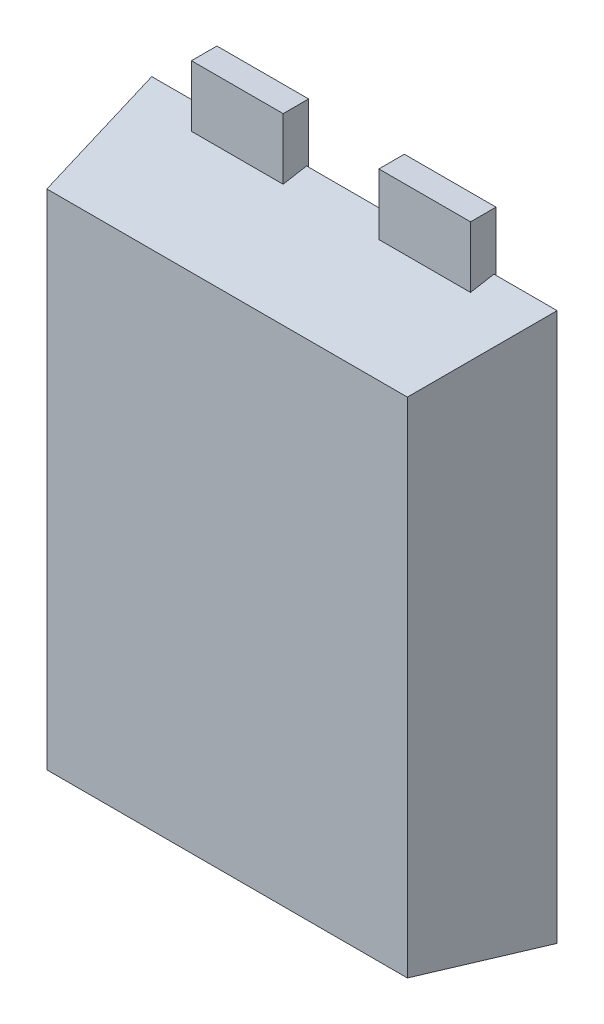
SolidWorks part; units mm, degrees
ref_plane "Front Plane" through (0, 0, 0) normal (0, 0, 1) x (1, 0, 0)
ref_plane "Top Plane" through (0, 0, 0) normal (0, 1, 0) x (1, 0, 0)
ref_plane "Right Plane" through (0, 0, 0) normal (1, 0, 0) x (0, 0, -1)
sketch "Sketch2" plane through (0, 0, 0) normal (0, 0, 1) x (1, 0, 0)
  line L22 (-1.525, 1.15) -> (-1.525, -2.4)
  line L23 (-1.525, -2.4) -> (-0.9, -2.4)
  line L24 (-0.9, -2.4) -> (-0.9, -3.25)
  line L25 (-0.9, -3.25) -> (-0.55, -3.25)
  line L26 (-0.55, -3.25) -> (-0.55, -3.05)
  line L27 (-0.55, -3.05) -> (0.55, -3.05)
  line L28 (0.55, -3.05) -> (0.55, -3.25)
  line L29 (0.55, -3.25) -> (0.9, -3.25)
  line L30 (0.9, -3.25) -> (0.9, -2.4)
  line L31 (0.9, -2.4) -> (1.525, -2.4)
  line L32 (1.525, -2.4) -> (1.525, 1.15)
  line L33 (1.525, 1.15) -> (-1.525, 1.15)
  line L34 (0, -0.9337) -> (0, 4.9794) construction
  line L35 (-1.37, 3.25) -> (-0.47, 3.25)
  line L36 (-1.37, 3.25) -> (-1.37, 2.4)
  line L37 (-1.37, 2.4) -> (-0.47, 2.4)
  line L38 (-0.47, 3.25) -> (-0.47, 2.4)
  line L39 (0.47, 3.25) -> (1.37, 3.25)
  line L40 (0.47, 3.25) -> (0.47, 2.4)
  line L41 (0.47, 2.4) -> (1.37, 2.4)
  line L42 (1.37, 3.25) -> (1.37, 2.4)
  point P2 (0, 1.15)
  point P24 (-0.92, 3.25)
  point P25 (0.92, 3.25)
  dimension "D1" = 3.05
  dimension "D2" = 3.55
  dimension "D3" = 0.85
  dimension "D4" = 1.8
  dimension "D5" = 0.35
  dimension "D6" = 0.2
  dimension "D7" = 3.25
  dimension "D8" = 1.25
  dimension "D9" = 6.5
  dimension "D10" = 0.9
  dimension "D11" = 1.84
extrude "Boss-Extrude1" add sketch "Sketch2" along normal blind 0.25
ref_plane "Plane1" through (0, 0, 0.02) normal (0, 0, 1) x (1, 0, 0)
sketch "Sketch3" plane through (0, 0, 0.02) normal (0, 0, 1) x (1, 0, 0)
  line L0 (-0.47, 3.25) -> (-1.37, 3.25) construction
  line L1 (-1.99, 2.69) -> (1.99, 2.69)
  line L2 (-1.99, 2.69) -> (-1.99, -2.69)
  line L3 (-1.99, -2.69) -> (1.99, -2.69)
  line L4 (1.99, 2.69) -> (1.99, -2.69)
  point P9 (0, 2.69)
  dimension "D1" = 5.38
  dimension "D2" = 3.98
  dimension "D3" = 0.56
extrude "Boss-Extrude2" add sketch "Sketch3" along normal blind 1.25
chamfer "Chamfer6" distance 1.25 angle 10 1 edges at (0, -2.69, 1.27) first distance on face at (0, -2.69, 0.39)
chamfer "Chamfer7" distance 1.25 angle 10 1 edges at (0, 2.69, 1.27) first distance on face at (0, 2.69, 0.645)
chamfer "Chamfer8" distance 1.25 angle 10 2 edges at (-1.99, 0, 1.27) (1.99, 0, 1.27) first distance on face at (-1.99, 0, 0.645) first distance on face at (1.99, 0, 0.645)
chamfer "Chamfer2" [suppressed] distance 1 angle 5
chamfer "Chamfer3" [suppressed] distance 0.4 angle 5
chamfer "Chamfer4" [suppressed] distance 0.5 angle 5
ref_plane "Plane2" through (0, 0.975, 0) normal (0, 1, 0) x (1, 0, 0)
sketch "Sketch4" plane through (0, 0.975, 0) normal (0, 1, 0) x (1, 0, 0)
  line L0 (-1.65, 0) -> (-1.25, 0)
  line L1 (-1.25, 0) -> (-1.15, -0.5)
  line L2 (-1.15, -0.5) -> (-0.8498, -0.5)
  line L3 (-0.8498, -0.5) -> (-0.8498, -0.65)
  line L4 (-0.8498, -0.65) -> (-1.273, -0.65)
  line L5 (-1.273, -0.65) -> (-1.373, -0.15)
  line L6 (-1.373, -0.15) -> (-1.65, -0.15)
  line L7 (-1.65, -0.15) -> (-1.65, 0)
  dimension "D1" = 0.15
  dimension "D2" = 0.15
  dimension "D3" = 0.5
  dimension "D4" = 1.65
  dimension "D5" = 0.4
  dimension "D6" = 0.1
extrude "Boss-Extrude3" [suppressed] add sketch "Sketch4" along normal mid plane 0.3
fillet "Fillet2" [suppressed] radius 0.1
fillet "Fillet3" [suppressed] radius 0.2
pattern_linear "LPattern1" [suppressed] count 4 spacing 0.65 of bodies 103
sketch "Sketch5" [suppressed] plane through (0, 0, 0.87) normal (0, 0, 1) x (1, 0, 0)
  line L1 (0.4785, 0.975) -> (-0.4785, 0.975) construction
  line L2 (1.4125, 1.615) -> (-1.065, 1.615) construction
  circle A0 centre (0.1738, 0.975) radius 0.25
  point P8 (0.1738, 1.615)
extrude "Cut-Extrude1" [suppressed] cut sketch "Sketch5" against normal blind 0.05
chamfer "Chamfer5" [suppressed] distance 0.05 angle 10
